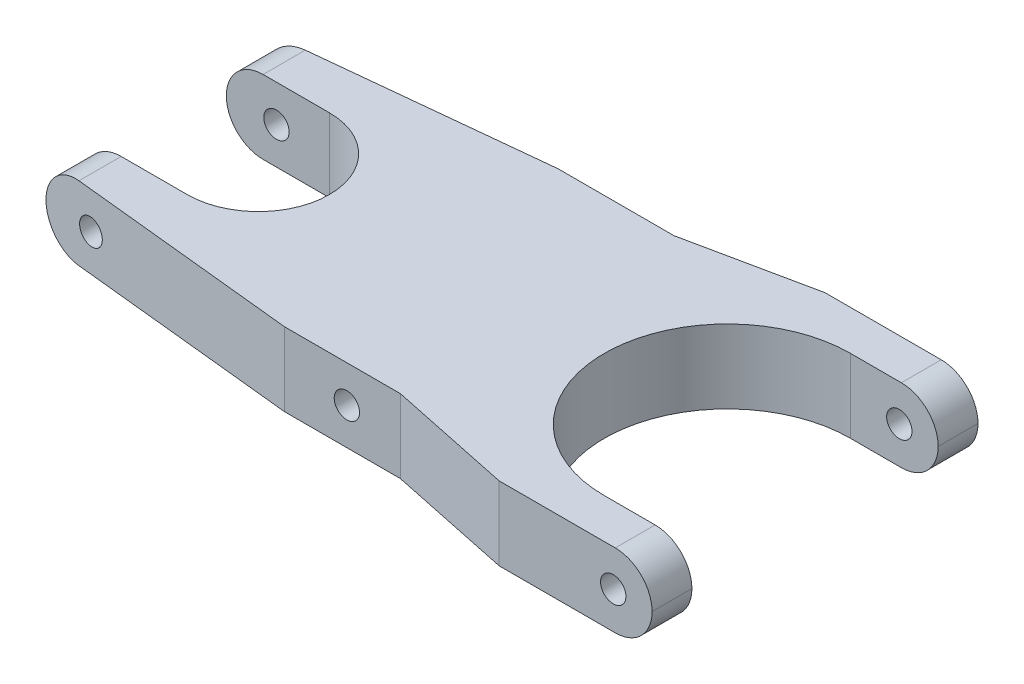
SolidWorks part; units mm, degrees
ref_plane "Front Plane" through (0, 0, 0) normal (0, 0, 1) x (1, 0, 0)
ref_plane "Top Plane" through (0, 0, 0) normal (0, 1, 0) x (1, 0, 0)
ref_plane "Right Plane" through (0, 0, 0) normal (1, 0, 0) x (0, 0, -1)
sketch "Sketch1" plane through (0, 0, 0) normal (0, 0, 1) x (1, 0, 0)
  line L0 (0, 0) -> (78.8, 0) construction
  circle A0 centre (0, 0) radius 1.75
  circle A1 centre (78.8, 0) radius 1.75
  circle A2 centre (38.4109, 0) radius 1.75
  dimension "D2" = 3.5
  dimension "D1" = 78.8
  dimension "D3" = 38.4109
sketch "Sketch2" plane through (0, 0, 0) normal (0, 0, 1) x (1, 0, 0)
  line L0 (0, 0) -> (78.8, 0) construction
  line L1 (-6.9218, -5.08) -> (84.1617, -5.08)
  line L2 (-6.9218, -5.08) -> (-6.9218, 5.08)
  line L3 (-6.9218, 5.08) -> (84.1617, 5.08)
  line L4 (84.1617, -5.08) -> (84.1617, 5.08)
  line L5 (0, 0) -> (78.8, 0) construction
  circle A0 centre (38.4109, 0) radius 1.75 construction
  circle A1 centre (0, 0) radius 1.75 construction
  circle A2 centre (78.8, 0) radius 1.75 construction
  circle A3 centre (38.4109, 0) radius 1.75
  circle A4 centre (0, 0) radius 1.75
  circle A5 centre (78.8, 0) radius 1.75
  point P15 (84.1617, 0)
  dimension "D1" = 10.16
extrude "Boss-Extrude1" add sketch "Sketch2" along normal mid plane 45
sketch "Sketch3" plane through (0, 5.08, 0) normal (0, 1, 0) x (1, 0, 0)
  line L0 (91.7243, 17) -> (72.0582, 17)
  line L1 (0, 0) -> (78.8, 0) construction
  line L2 (72.0582, -17) -> (91.7243, -17)
  line L3 (91.7243, -17) -> (91.7243, 17)
  line L4 (-6.9218, 15.0978) -> (29.792, 18.8883)
  line L5 (-35.2672, 9.8) -> (7.2968, 9.8)
  line L6 (-35.2672, 9.8) -> (-35.2672, -9.8)
  line L7 (-35.2672, -9.8) -> (7.2968, -9.8)
  line L8 (-6.9218, -22.5) -> (-6.9218, 22.5) construction
  line L9 (29.792, 18.8883) -> (45.8, 18.8883)
  line L10 (45.8, 18.8883) -> (63.048, 22.5)
  line L11 (84.1617, 22.5) -> (-6.9218, 22.5) construction
  line L12 (63.048, 22.5) -> (63.048, 41.5638)
  line L13 (63.048, 41.5638) -> (-6.9218, 41.5638)
  line L14 (-6.9218, 41.5638) -> (-6.9218, 15.0978)
  line L15 (0, 0) -> (-40.8513, 0) construction
  line L16 (63.048, -22.5) -> (63.048, -41.5638)
  line L17 (45.8, -18.8883) -> (63.048, -22.5)
  line L18 (29.792, -18.8883) -> (45.8, -18.8883)
  line L19 (-6.9218, -15.0978) -> (29.792, -18.8883)
  line L20 (-6.9218, -41.5638) -> (-6.9218, -15.0978)
  line L21 (63.048, -41.5638) -> (-6.9218, -41.5638)
  arc A0 (72.0582, 17) -> (72.0582, -17) centre (72.0582, 0) ccw
  arc A1 (7.2968, 9.8) -> (7.2968, -9.8) centre (7.2968, 0) cw
  dimension "D1" = 34
  dimension "D2" = 19.6661
  dimension "D3" = 19.6
extrude "Cut-Extrude1" cut sketch "Sketch3" against normal through all
fillet "Fillet1" radius 5.08 8 edges at (-6.9218, 5.08, -12.4489) (-6.9218, -5.08, -12.4489) (-6.9218, -5.08, 12.4489) (-6.9218, 5.08, 12.4489) (84.1617, -5.08, -19.75) (84.1617, -5.08, 19.75) (84.1617, 5.08, 19.75) (84.1617, 5.08, -19.75)
